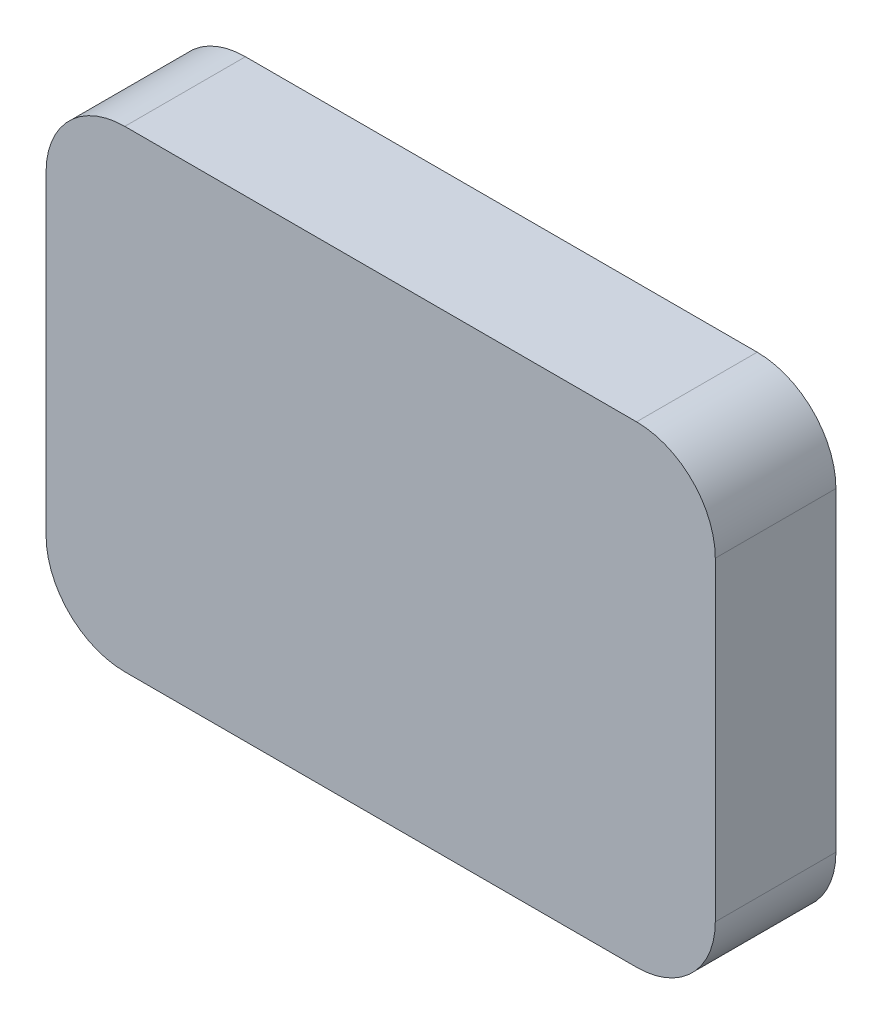
SolidWorks part; units mm, degrees
ref_plane "Plan de face" through (0, 0, 0) normal (0, 0, 1) x (1, 0, 0)
ref_plane "Plan de dessus" through (0, 0, 0) normal (0, 1, 0) x (1, 0, 0)
ref_plane "Plan de droite" through (0, 0, 0) normal (1, 0, 0) x (0, 0, -1)
sketch "Esquisse1" plane through (0, 0, 0) normal (0, 0, 1) x (1, 0, 0)
  line L1 (-32.5, 30) -> (32.5, 30)
  line L2 (-42.5, 20) -> (-42.5, -20)
  line L3 (-32.5, -30) -> (32.5, -30)
  line L4 (42.5, 20) -> (42.5, -20)
  line L5 (-42.5, 30) -> (42.5, -30) construction
  line L6 (-42.5, -30) -> (42.5, 30) construction
  arc A0 (-42.5, -20) -> (-32.5, -30) centre (-32.5, -20) ccw
  arc A1 (32.5, -30) -> (42.5, -20) centre (32.5, -20) ccw
  arc A2 (32.5, 30) -> (42.5, 20) centre (32.5, 20) cw
  arc A3 (-32.5, 30) -> (-42.5, 20) centre (-32.5, 20) ccw
  point P0 (0, 0)
  dimension "D1" = 10
  dimension "D2" = 65
  dimension "D3" = 40
sketch "profil" plane through (0, 0, 0) normal (1, 0, 0) x (0, 0, -1)
  line L0 (0, -28.4) -> (4.1391, -28.4)
  line L1 (4.1391, -28.4) -> (14.1228, -23.8)
  line L3 (14.1228, -30) -> (0, -30)
  line L4 (0, -30) -> (0, -28.4)
  line L6 (0, -20) -> (0, -30) construction
  line L7 (0, -30) -> (0, 30) construction
  line L8 (14.1228, -23.8) -> (14.1228, -25.4)
  line L9 (14.1228, -28.4) -> (14.1228, -30)
  arc A1 (14.1228, -25.4) -> (14.1228, -28.4) centre (14.1228, -26.9) cw
  point P0 (4.1391, -28.4)
  dimension "D1" = 3
  dimension "D2" = 1.6
  dimension "D3" = 14.1228
sweep "Balayage1" add profiles "profil" path "Esquisse1"
extrude "Boss.-Extru.1" add sketch "Esquisse1<3>" along normal blind 1.2
sketch "Esquisse1<3>" plane through (0, 0, 0) normal (0, 0, 1) x (1, 0, 0) same geometry as "Esquisse1"
fillet "Congé1" radius 2 9 edges at (-38.4397, 25.9397, 0) (-40.9, 0, 0) (-38.4397, -25.9397, 0) (-16.25, -28.4, 0) (16.25, -28.4, 0) (38.4397, -25.9397, 0) (40.9, 0, 0) (38.4397, 25.9397, 0) (0, 28.4, 0)
equation "\"buse\"=0.4"
equation "\"coque\"= \"buse\" * 4"
equation "\"diam_silicone\"=3"
equation "\"D1@profil\" = \"diam_silicone\""
equation "\"couche\"=0.2"
equation "\"D1@Boss.-Extru.1\"=\"fond\""
equation "\"fond\"= \"couche\" * 6"
equation "\"D2@Esquisse1\"=\"dim_ext_L@boitier_balaye-1.Part\""
equation "\"D3@profil\"=\"hauteur_boitier@boitier_balaye-1.Part\""
